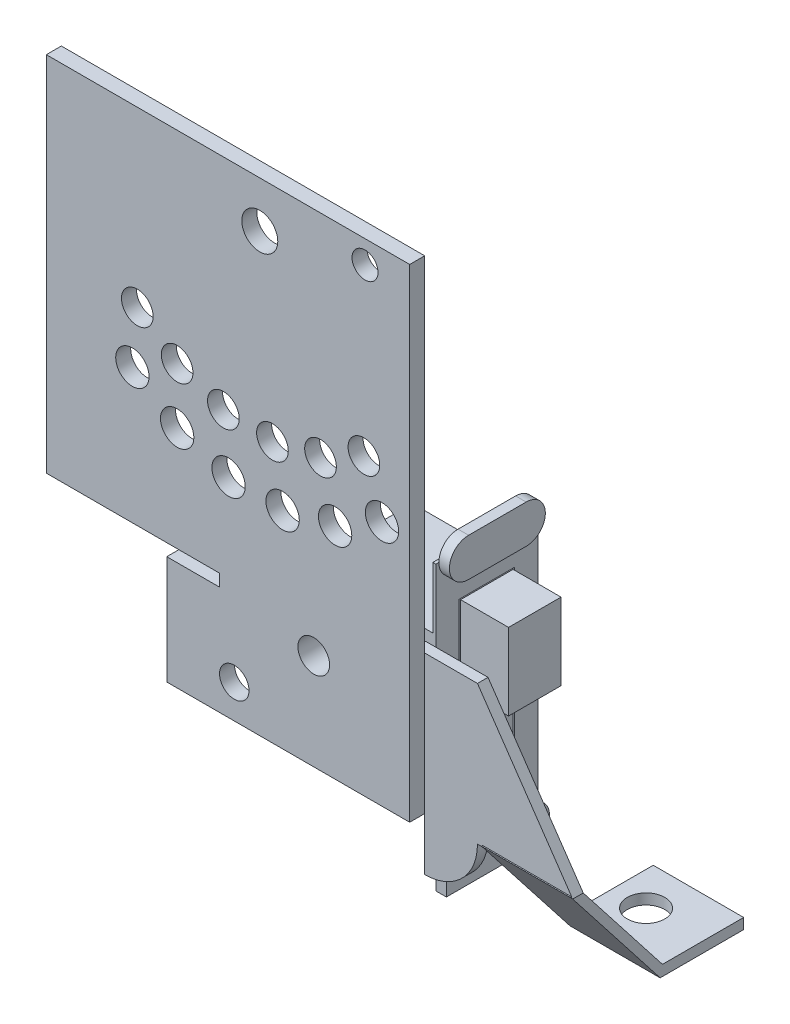
SolidWorks part; units mm, degrees
ref_plane "Front Plane" through (0, 0, 0) normal (0, 0, 1) x (1, 0, 0)
ref_plane "Top Plane" through (0, 0, 0) normal (0, 1, 0) x (1, 0, 0)
ref_plane "Right Plane" through (0, 0, 0) normal (1, 0, 0) x (0, 0, -1)
sketch "Sketch1" plane through (0, 0, 0) normal (0, 0, 1) x (1, 0, 0)
  line L0 (3.3633, 19.1897) -> (3.3633, -31.9659) construction
  line L1 (-19.2383, -19.1897) -> (19.2383, -19.1897)
  line L2 (-19.2383, -19.1897) -> (-19.2383, 19.1897)
  line L3 (-19.2383, 19.1897) -> (19.2383, 19.1897)
  line L4 (19.2383, -19.1897) -> (19.2383, 19.1897)
  line L5 (-19.2383, -19.1897) -> (19.2383, 19.1897) construction
  line L6 (-19.2383, 19.1897) -> (19.2383, -19.1897) construction
  line L7 (19.2383, -19.1897) -> (-6.4875, -19.1897)
  line L8 (19.2383, -19.1897) -> (19.2383, -31.9659)
  line L9 (19.2383, -31.9659) -> (-6.4875, -31.9659)
  line L10 (-6.4875, -19.1897) -> (-6.4875, -31.9659)
  line L11 (-6.4875, -19.1897) -> (-0.8995, -19.1897)
  line L12 (-6.4875, -19.1897) -> (-6.4875, -20.4724)
  line L13 (-6.4875, -20.4724) -> (-0.8995, -20.4724)
  line L14 (-0.8995, -19.1897) -> (-0.8995, -20.4724)
  circle A2 centre (3.3633, 14.3091) radius 1.905
  circle A3 centre (14.5075, 16.7756) radius 1.3779
  point P0 (0, 0)
  dimension "D8" = 3.81
  dimension "D9" = 15.875
  dimension "D10" = 2.7559
  dimension "D11" = 4.7307
  dimension "D1" = 38.3794
  dimension "D2" = 1.2827
  dimension "D3" = 11.4935
  dimension "D12" = 12.7508
  dimension "D13" = 5.588
extrude "Boss-Extrude1" add sketch "Sketch1" along normal blind 1.5875 contours L7 L14 L13 L10 L9 L8 | L1 L7 L4 L3 L2 A3 A2 region at (-0.0856, -0.1804, 0) region at (6.5999, -25.7059, 0)
sketch "Sketch2" plane through (0, 0, 1.5875) normal (0, 0, 1) x (1, 0, 0)
  line L0 (3.3633, 14.3091) -> (3.3633, -31.9659) construction
  line L1 (19.2383, -31.9659) -> (-6.4875, -31.9659) construction
  line L2 (19.2383, 19.1897) -> (19.2383, -31.9659) construction
  line L3 (-6.4875, -20.4724) -> (-6.4875, -31.9659) construction
  circle A0 centre (16.3046, -5.8833) radius 1.7653
  circle A1 centre (14.3869, -0.8033) radius 1.6764
  circle A2 centre (9.7943, -3.2564) radius 1.6764
  circle A3 centre (4.7035, -4.3485) radius 1.6764
  circle A4 centre (-0.4912, -3.9952) radius 1.6764
  circle A5 centre (-5.3872, -2.2237) radius 1.6764
  circle A6 centre (-9.6053, 0.8287) radius 1.6764
  circle A8 centre (11.3396, -8.7371) radius 1.7653
  circle A9 centre (5.7804, -10.1118) radius 1.7653
  circle A10 centre (0.0576, -9.901) radius 1.7653
  circle A11 centre (-5.3854, -8.1209) radius 1.7653
  circle A12 centre (-10.1269, -4.9095) radius 1.7653
  circle A15 centre (9.0783, -21.7805) radius 1.6764
  circle A16 centre (0.6626, -28.4099) radius 1.5621
  point P24 (3.3633, 14.3091)
  point P36 (3.6691, 10.3535)
  dimension "D1" = 3.3528
  dimension "D2" = 3.5306
  dimension "D3" = 2.9337
  dimension "D4" = 4.8514
  dimension "D7" = 5.08
  dimension "D8" = 3.3528
  dimension "D9" = 3.1242
  dimension "D10" = 10.16
  dimension "D11" = 10.1854
  dimension "D12" = 3.556
  dimension "D13" = 7.1501
  dimension "D5" = 6
  dimension "D6" = 6
extrude "Cut-Extrude1" cut sketch "Sketch2" against normal up to next
sketch "Sketch3" plane through (0, 0, 0) normal (0, 0, -1) x (-1, 0, 0)
  line L0 (-24.8263, -31.9659) -> (-34.9101, -31.9659)
  line L1 (-6.0303, -18.7579) -> (-18.2223, -18.7579)
  line L2 (-6.0303, -18.7579) -> (-6.0303, -30.4419)
  line L3 (-6.0303, -30.4419) -> (-18.2223, -30.4419)
  line L4 (-18.2223, -18.7579) -> (-18.2223, -30.4419)
  line L9 (-19.2383, -31.9659) -> (6.4875, -31.9659) construction
  line L10 (-18.2223, -17.2339) -> (-24.8263, -17.2339)
  line L11 (-18.2223, -17.2339) -> (-18.2223, -31.9659)
  line L12 (-18.2223, -31.9659) -> (-24.8263, -31.9659)
  line L13 (-24.8263, -17.2339) -> (-24.8263, -31.9659)
  line L14 (-34.9101, -31.9659) -> (-24.8263, -17.2339)
  line L15 (-19.2383, -31.9659) -> (-19.2383, -37.5539)
  line L16 (-24.8263, -17.2339) -> (-24.8263, -31.9659)
  line L17 (-24.8263, -31.9659) -> (-19.2383, -31.9659)
  arc A0 (-24.8263, -31.9659) -> (-19.2383, -37.5539) centre (-19.2383, -31.9659) ccw
  circle M12 centre (-9.0783, -21.7805) radius 1.6764
  line M24 (-19.2383, 19.1897) -> (-19.2383, -31.9659)
  dimension "D8" = 5.588
  dimension "D1" = 11.684
  dimension "D2" = 12.192
  dimension "D3" = 14.732
  dimension "D4" = 0
  dimension "D5" = 1.524
  dimension "D6" = 6.604
  dimension "D7" = 10.0838
extrude "Boss-Extrude2" add sketch "Sketch3" along normal blind 1.1176 contours L14 L0 L13 | L10 L13 L12 M24 | L1 L4 L3 L2 M12 | L12 A0 L15 | L11 L10 L13 L12 region at (22.0323, -24.5999, 0) region at (28.1875, -27.0552, 0) region at (21.6099, -34.3375, 0) region at (12.3277, -24.7862, 0)
ref_plane "Plane1" through (0, 0, -0.5588) normal (0, 0, 1) x (1, 0, 0)
ref_axis "Axis1" through (34.9101, -31.9659, -0.5588) along (-1, 0, 0)
ref_plane "Plane2" through (0, -20.1207, -15.72) normal (0, 0.788, 0.6157) x (-1, 0, 0)
sketch "Sketch4" plane through (0, -20.1207, -15.72) normal (0, 0.788, 0.6157) x (-1, 0, 0)
  line L0 (-34.9101, 19.2398) -> (-24.8263, 19.2398) construction
  line L1 (-25.3343, 19.6802) -> (-34.9101, 19.6802)
  line L2 (-25.3343, 19.6802) -> (-25.3343, 18.7995)
  line L3 (-25.3343, 18.7995) -> (-34.9101, 18.7995)
  line L4 (-34.9101, 19.6802) -> (-34.9101, 18.7995)
  line L5 (-25.3343, 19.6802) -> (-34.9101, 18.7995) construction
  line L6 (-25.3343, 18.7995) -> (-34.9101, 19.6802) construction
  point P0 (-30.1222, 19.2398)
  dimension "D1" = 9.5758
extrude "Boss-Extrude3" add sketch "Sketch4" against normal blind 14.732 and the other way blind 0.4572
sketch "Sketch7" plane through (0, 0, -1.1176) normal (0, 0, -1) x (-1, 0, 0)
  line L0 (-34.4779, -31.3345) -> (-34.9101, -31.3345)
  line L1 (-34.9101, -31.3345) -> (-34.9101, -31.9659)
  line L2 (-34.9101, -31.9659) -> (-34.4779, -31.3345)
extrude "Cut-Extrude4" cut sketch "Sketch7" against normal through all
ref_axis "Axis2" through (25.3343, -43.3038, -9.9757) along (1, 0, 0)
ref_plane "Plane3" through (0, 0, -9.9757) normal (0, 0, 1) x (1, 0, 0)
sketch "Sketch8" plane through (0, 0, -9.9757) normal (0, 0, 1) x (1, 0, 0)
  line L11 (34.9101, -42.7046) -> (25.3343, -42.7046)
  line L12 (34.9101, -42.7046) -> (34.9101, -43.8222)
  line L13 (34.9101, -43.8222) -> (25.3343, -43.8222)
  line L14 (25.3343, -42.7046) -> (25.3343, -43.8222)
  line L15 (34.9101, -42.7046) -> (25.3343, -43.8222) construction
  line L16 (34.9101, -43.8222) -> (25.3343, -42.7046) construction
  point P0 (30.1222, -43.2634)
  dimension "D1" = 1.1176
  dimension "D2" = 9.5758
extrude "Boss-Extrude5" add sketch "Sketch8" against normal blind 8.128 and the other way blind 0.7112
sketch "Sketch9" plane through (0, 0, -1.1176) normal (0, 0, -1) x (-1, 0, 0)
  line L0 (-18.2223, -31.9659) -> (6.4875, -31.9659) construction
  line L1 (-6.0303, -31.9659) -> (-18.9843, -31.9659)
  line L2 (-6.0303, -31.9659) -> (-6.0303, -16.0909)
  line L3 (-6.0303, -16.0909) -> (-18.9843, -16.0909)
  line L4 (-18.9843, -31.9659) -> (-18.9843, -16.0909)
  line L6 (-18.9843, -10.8839) -> (-19.2383, -10.8839)
  line L7 (-18.9843, -10.8839) -> (-18.9843, -37.5539)
  line L8 (-18.9843, -37.5539) -> (-19.2383, -37.5539)
  line L9 (-19.2383, -10.8839) -> (-19.2383, -37.5539)
  dimension "D1" = 15.875
  dimension "D2" = 26.67
  dimension "D3" = 0.254
  dimension "D4" = 12.954
extrude "Boss-Extrude10" add sketch "Sketch9" along normal blind 10.795 contours L2 L1 L4 L3
sketch "Sketch10" plane through (0, 0, -1.1176) normal (0, 0, -1) x (-1, 0, 0)
  line L0 (-18.9843, -17.2339) -> (-18.9843, -16.0909) construction
  line L5 (-19.3018, -37.5535) -> (-18.9843, -37.5535)
  line L6 (-19.3018, -37.5535) -> (-19.3018, -9.6135)
  line L7 (-19.3018, -9.6135) -> (-18.9843, -9.6135)
  line L8 (-18.9843, -37.5535) -> (-18.9843, -9.6135)
  arc A0 (-24.8263, -31.9659) -> (-19.2383, -37.5539) centre (-19.2383, -31.9659) ccw construction
  dimension "D1" = 27.94
  dimension "D2" = 0.3175
extrude "Boss-Extrude12" add sketch "Sketch10" along normal blind 10.795
sketch "Sketch11" plane through (19.3018, 0, 0) normal (1, 0, 0) x (0, 0, -1)
  line L5 (6.5151, -9.6135) -> (6.5151, -37.5535) construction
  line L6 (11.9126, -9.6135) -> (1.1176, -9.6135) construction
  line L7 (11.9126, -37.5535) -> (1.1176, -37.5535) construction
  line L9 (3.737, -22.3122) -> (9.2932, -22.3122)
  line L10 (3.737, -22.3122) -> (3.737, -14.1842)
  line L11 (3.737, -14.1842) -> (9.2932, -14.1842)
  line L12 (9.2932, -22.3122) -> (9.2932, -14.1842)
  line L13 (3.737, -22.3122) -> (9.2932, -14.1842) construction
  line L14 (3.737, -14.1842) -> (9.2932, -22.3122) construction
  point P6 (6.5151, -18.2482)
  dimension "D1" = 8.128
  dimension "D2" = 5.5562
extrude "Boss-Extrude13" add sketch "Sketch11" along normal blind 5.08
sketch "Sketch12" plane through (19.3018, 0, 0) normal (1, 0, 0) x (0, 0, -1)
  line L0 (6.5151, -9.6135) -> (6.5151, -37.5535) construction
  line L1 (11.9126, -9.6135) -> (1.1176, -9.6135) construction
  line L2 (11.9126, -37.5535) -> (1.1176, -37.5535) construction
  line L4 (3.5941, -33.1085) -> (9.4361, -33.1085)
  line L5 (3.5941, -33.1085) -> (3.5941, -14.0585)
  line L6 (3.5941, -14.0585) -> (9.4361, -14.0585)
  line L7 (9.4361, -33.1085) -> (9.4361, -14.0585)
  line L8 (3.5941, -33.1085) -> (9.4361, -14.0585) construction
  line L9 (3.5941, -14.0585) -> (9.4361, -33.1085) construction
  point P6 (6.5151, -23.5835)
  dimension "D1" = 5.842
  dimension "D2" = 19.05
extrude "Cut-Extrude5" cut sketch "Sketch12" against normal blind 0.127
sketch "Sketch13" plane through (19.3018, 0, 0) normal (1, 0, 0) x (0, 0, -1)
  line L0 (11.9126, -37.5535) -> (1.1176, -37.5535) construction
  line L1 (3.4671, -9.6135) -> (9.5631, -9.6135) construction
  line L2 (10.0076, -35.5215) -> (1.1176, -35.5215)
  line L3 (1.1176, -37.5535) -> (1.1176, -31.9659) construction
  line L4 (1.1176, -35.5215) -> (1.1176, -39.5855)
  line L5 (1.1176, -39.5855) -> (10.0076, -39.5855)
  line L6 (11.9126, -9.6135) -> (1.1176, -9.6135) construction
  line L7 (3.4671, -7.5815) -> (9.5631, -7.5815)
  line L8 (3.4671, -11.6455) -> (9.5631, -11.6455)
  arc A0 (10.0076, -35.5215) -> (10.0076, -39.5855) centre (10.0076, -37.5535) cw
  arc A1 (3.4671, -7.5815) -> (3.4671, -11.6455) centre (3.4671, -9.6135) ccw
  arc A2 (9.5631, -11.6455) -> (9.5631, -7.5815) centre (9.5631, -9.6135) ccw
  point P13 (6.5151, -9.6135)
  dimension "D1" = 2.032
  dimension "D3" = 2.032
  dimension "D2" = 6.096
  dimension "D4" = 8.89
extrude "Boss-Extrude14" add sketch "Sketch13" along normal blind 1.1176
sketch "Sketch14" plane through (0, -42.7046, 0) normal (0, 1, 0) x (1, 0, 0)
  line L1 (34.9101, 18.1037) -> (25.3343, 18.1037) construction
  line L2 (25.3343, 9.5076) -> (25.3343, 18.1037) construction
  circle A0 centre (28.8903, 13.7857) radius 1.9844
  dimension "D1" = 3.9688
  dimension "D2" = 3.556
  dimension "D3" = 4.318
extrude "Cut-Extrude6" cut sketch "Sketch14" against normal through all
